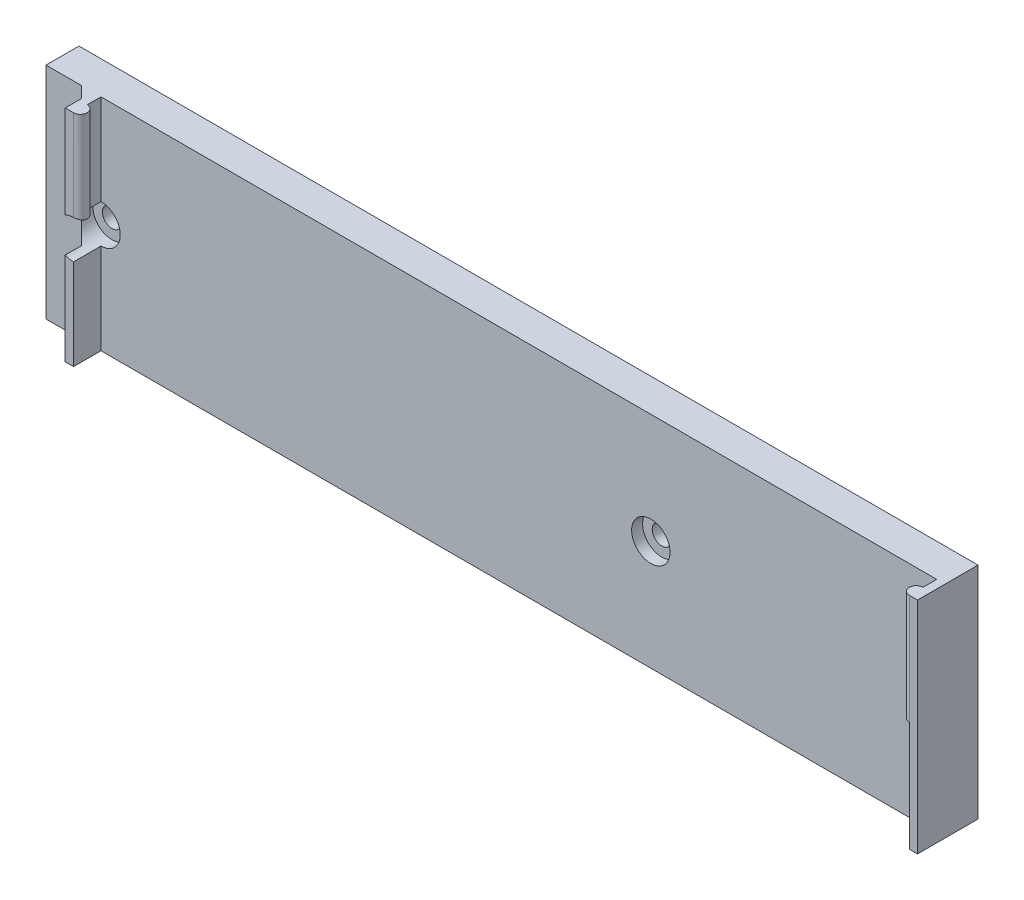
SolidWorks part; units mm, degrees
ref_plane "Piano frontale" through (0, 0, 0) normal (0, 0, 1) x (1, 0, 0)
ref_plane "Piano superiore" through (0, 0, 0) normal (0, 1, 0) x (1, 0, 0)
ref_plane "Piano destro" through (0, 0, 0) normal (1, 0, 0) x (0, 0, -1)
sketch "Schizzo1" plane through (0, 0, 0) normal (0, 0, 1) x (1, 0, 0)
  line L1 (77.5, -35) -> (-77.5, -35)
  line L2 (77.5, -35) -> (77.5, 35)
  line L3 (77.5, 35) -> (-77.5, 35)
  line L4 (-77.5, -35) -> (-77.5, 35)
  line L5 (77.5, -35) -> (-77.5, 35) construction
  line L6 (77.5, 35) -> (-77.5, -35) construction
  point P0 (0, 0)
  dimension "D1" = 155
  dimension "D2" = 70
extrude "Estrusione-Estrusione1" add sketch "Schizzo1" along normal blind 6
sketch "Schizzo3" plane through (0, 0, 6) normal (0, 0, 1) x (1, 0, 0)
  line L0 (-76, 35) -> (-76, -33.5)
  line L1 (-76, -33.5) -> (76, -33.5)
  line L2 (76, -33.5) -> (76, 35)
  line L3 (-77.5, 35) -> (-76, 35)
  line L4 (-77.5, 35) -> (-77.5, -35)
  line L5 (-77.5, -35) -> (77.5, -35)
  line L6 (77.5, -35) -> (77.5, 35)
  line L7 (77.5, 35) -> (-77.5, 35)
  line L8 (-77.5, 35) -> (-77.5, -35)
  line L9 (-77.5, -35) -> (77.5, -35)
  line L10 (77.5, -35) -> (77.5, 35)
  line L11 (77.5, 35) -> (76, 35)
  line L12 (-76, -33.5) -> (-76, -35)
  line L13 (76, -33.5) -> (76, -35)
  line M5 (-77.5, 35) -> (-77.5, -35)
  line M6 (-77.5, -35) -> (77.5, -35)
  line M7 (77.5, -35) -> (77.5, 35)
  line M8 (77.5, 35) -> (-77.5, 35)
  dimension "D1" = 0
  dimension "D2" = 1.5
extrude "Estrusione-Estrusione3" add sketch "Schizzo3" along normal blind 5 contours L12 L0 M8 M5 M6 | L2 L13 M6 M7 M8 region at (-76.75, 0, 6) region at (76.75, 0, 6)
sketch "Schizzo4" plane through (0, 35, 0) normal (0, 1, 0) x (1, 0, 0)
  line L3 (76, -11) -> (76, -8.5)
  line L4 (76, -11) -> (76, -6) construction
  arc A1 (76, -8.5) -> (76, -11) centre (76, -9.75) ccw
  line M11 (76, -6) -> (76, -11)
extrude "Estrusione-Estrusione4" add sketch "Schizzo4" against normal blind 20 contours M11 region at (75.4695, 35, 9.75)
mirror "Specchia1" about plane through (0, 0, 0) normal (1, 0, 0) of "Estrusione-Estrusione4"
sketch "Schizzo6" plane through (0, 0, 0) normal (0, 0, 1) x (1, 0, 0)
  line L6 (-77.5, -35) -> (77.5, -35) construction
  line L7 (77.5, 35) -> (-86, 35)
  line L8 (77.5, 35) -> (77.5, -35)
  line L9 (77.5, -35) -> (-86, -35)
  line L10 (-86, 35) -> (-86, -35)
  line L11 (-76, 15) -> (-76, -35) construction
  dimension "D1" = 10
extrude "Estrusione-Estrusione5" add sketch "Schizzo6" along normal up to surface (6 mm away) contours L7 L10 L9 region at (-4.25, 0, 0) up to face at (0, 0, 6)
sketch "Schizzo7" plane through (0, 0, 0) normal (0, 0, -1) x (-1, 0, 0)
  line L0 (-24, 15) -> (76, 15) construction
  line L1 (86, 35) -> (86, -35) construction
  line L2 (86, -35) -> (-77.5, -35) construction
  circle A0 centre (-24, 15) radius 1.75
  circle A1 centre (76, 15) radius 1.75
  dimension "D4" = 3.5
  dimension "D1" = 100
  dimension "D2" = 10
  dimension "D3" = 50
extrude "Taglio-Estrusione2" cut sketch "Schizzo7" against normal through all
hole_wizard "Foro1" positions "Schizzo3D1" profile "Schizzo8" legacy end condition through all
sketch3d "Schizzo3D1"
  line L0 (24, 15, 6) -> (24, 15, 0) construction
  line L1 (-76, 15, 11) -> (-76, 15, 6) construction
  point P0 (24, 15, 6)
  point P4 (-76, 15, 6)
sketch "Schizzo8" plane through (24, 15, 6) normal (1, 0, 0) x (0, -1, 0)
  line L0 (0, 0) -> (0, 7.0515)
  line L1 (0, 7.0515) -> (1.75, 6)
  line L2 (1.75, 6) -> (1.75, 2)
  line L3 (1.75, 2) -> (3.5, 2)
  line L4 (3.5, 0) -> (0, 0)
  line L5 (0, -11.3109) -> (0, 121.1557) construction
  line L6 (0, 7.0515) -> (-1.75, 6) construction
  line L7 (3.5, 2) -> (3.5, 0)
  dimension "Depth" = 6
  dimension "Drill Angle" = 118
  dimension "Diameter" = 3.5
  dimension "C-Bore Diameter" = 7
  dimension "C-Bore Depth" = 2
sketch "Schizzo9" plane through (0, 0, 4) normal (0, 0, 1) x (1, 0, 0)
  circle A1 centre (-76, 15) radius 3.5
  circle A2 centre (-76, 15) radius 3.5
  dimension "D1" = 0
extrude "Taglio-Estrusione3" cut sketch "Schizzo9" along normal through all
chamfer "Smusso1" distance 2 angle 45 2 edges at (-77.5, 26.5811, 6) (-77.5, -11.5811, 6)
sketch "Schizzo10" plane through (0, -35, 0) normal (0, -1, 0) x (1, 0, 0)
  line L11 (76, 11) -> (76, 6)
  line L12 (76, 6) -> (-76, 6)
  line L13 (-76, 6) -> (-76, 11)
  line L14 (-76, 11) -> (-77.5, 11)
  line L15 (-77.5, 11) -> (-77.5, 8)
  line L16 (-77.5, 8) -> (-79.5, 6)
  line L17 (-79.5, 6) -> (-86, 6)
  line L18 (-86, 6) -> (-86, 0)
  line L19 (-86, 0) -> (77.5, 0)
  line L20 (77.5, 0) -> (77.5, 11)
  line L21 (77.5, 11) -> (76, 11)
  line L22 (76, 11) -> (76, 6)
  line L23 (76, 6) -> (-76, 6)
  line L24 (-76, 6) -> (-76, 11)
  line L25 (-76, 11) -> (-77.5, 11)
  line L26 (-77.5, 11) -> (-77.5, 8)
  line L27 (-77.5, 8) -> (-79.5, 6)
  line L28 (-79.5, 6) -> (-86, 6)
  line L29 (-86, 6) -> (-86, 0)
  line L30 (-86, 0) -> (77.5, 0)
  line L31 (77.5, 0) -> (77.5, 11)
  line L32 (77.5, 11) -> (76, 11)
  dimension "D1" = 0
extrude "Taglio-Estrusione4" cut sketch "Schizzo10" against normal blind 30
